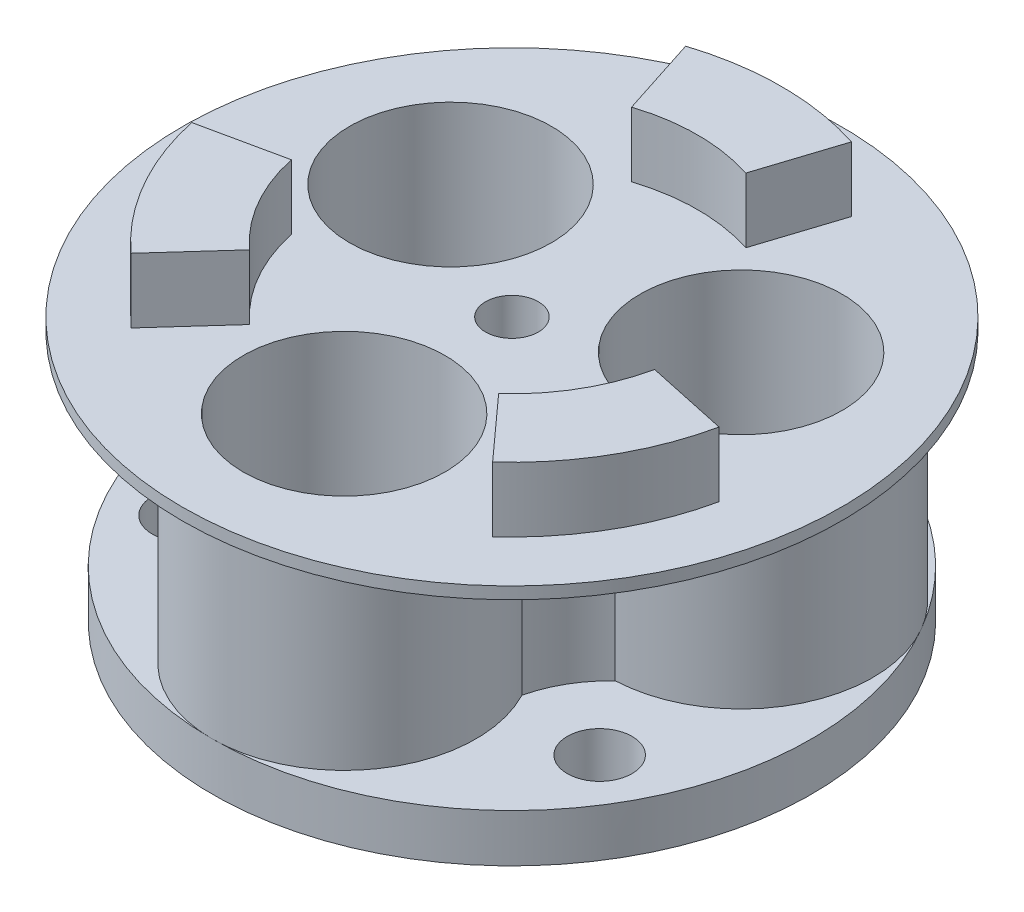
SolidWorks part; units mm, degrees
ref_plane "Front Plane" through (0, 0, 0) normal (0, 0, 1) x (1, 0, 0)
ref_plane "Top Plane" through (0, 0, 0) normal (0, 1, 0) x (1, 0, 0)
ref_plane "Right Plane" through (0, 0, 0) normal (1, 0, 0) x (0, 0, -1)
sketch "Sketch1" plane through (0, 0, 0) normal (0, 1, 0) x (1, 0, 0)
  line L0 (0, -55) -> (0, 55) construction
  circle A0 centre (0, 0) radius 27.5
  circle A1 centre (0, 0) radius 2.2
  circle A2 centre (0, -14) radius 8.425
  circle A3 centre (-12.1244, 7) radius 8.425
  circle A4 centre (12.1244, 7) radius 8.425
  point P14 (0, 0)
  dimension "D1" = 55
  dimension "D2" = 4.4
  dimension "D3" = 16.85
  dimension "D4" = 14
  dimension "D5" = 3
extrude "Boss-Extrude1" add sketch "Sketch1" along normal blind 22
ref_plane "Plane1" through (0, 4, 0) normal (0, 1, 0) x (1, 0, 0)
sketch "Sketch4" plane through (0, 22, 0) normal (0, 1, 0) x (1, 0, 0)
  line L0 (0, 0) -> (23.6709, -13.6664) construction
  line L1 (-22.0001, -4.7164) -> (-15.1556, -3.2491)
  line L2 (0, -55) -> (0, 55) construction
  line L3 (15.0846, -16.6945) -> (10.3916, -11.5006)
  line L4 (22.0001, -4.7164) -> (15.1556, -3.2491)
  line L5 (-15.0846, -16.6945) -> (-10.3916, -11.5006)
  line L6 (6.9155, 21.4109) -> (4.764, 14.7497)
  line L7 (-6.9155, 21.4109) -> (-4.764, 14.7497)
  circle A0 centre (0, 0) radius 22.5
  circle A2 centre (0, 0) radius 15.5
  point P23 (-1.3727, 0.446)
  point P24 (0, 0)
  dimension "D1" = 45
  dimension "D2" = 7
  dimension "D3" = 60
  dimension "D4" = 35.8
  dimension "D5" = 3
extrude "Boss-Extrude2" add sketch "Sketch4" along normal blind 5.4 contours A2 A0 | A2 A0 | L0 A2 L3 A0 | A2 L0 A0 L4 region at (17.8598, 22, 6.8736) region at (14.8826, 22, 12.0302) region at (-16.3712, 22, 9.4519) region at (0, 22, -18.9039)
sketch "Sketch5" plane through (0, 4, 0) normal (0, 1, 0) x (1, 0, 0)
  circle A0 centre (-12.1244, 7) radius 11
  circle A1 centre (0, 0) radius 22.5 construction
  circle A2 centre (0, 22.5) radius 10
  circle A3 centre (0, 0) radius 40.9893
  circle A4 centre (12.1244, 7) radius 11
  circle A5 centre (19.4856, -11.25) radius 10
  circle A6 centre (0, -14) radius 11
  circle A7 centre (-19.4856, -11.25) radius 10
  point P20 (0, 0)
  dimension "D1" = 22
  dimension "D2" = 20
  dimension "D3" = 45
  dimension "D4" = 3
extrude "Cut-Extrude1" cut sketch "Sketch5" along normal blind 17 contours A3 A7 A0 A2 A4 A5 A6 | A6 A5 A4 | A4 A2 A0 | A6 A7 A0 region at (0, 4, -22.8169) region at (-19.76, 4, 11.4085) region at (19.76, 4, 11.4085) region at (-39.8299, 4, 0)
sketch "Sketch6" plane through (0, 0, 0) normal (0, -1, 0) x (1, 0, 0)
  circle A0 centre (0, 0) radius 20 construction
  circle A1 centre (0, -20) radius 2.7
  circle A2 centre (-17.3205, 10) radius 2.7
  circle A3 centre (17.3205, 10) radius 2.7
  point P11 (0, 0)
  dimension "D1" = 40
  dimension "D2" = 5.4
  dimension "D3" = 3
extrude "Cut-Extrude2" cut sketch "Sketch6" against normal blind 5
sketch "Sketch7" plane through (0, 0, 0) normal (0, -1, 0) x (1, 0, 0)
  circle A0 centre (0, 0) radius 25
  circle A2 centre (0, 0) radius 33.7565
  circle M6 centre (0, 0) radius 27.5
  dimension "D1" = 50
extrude "Cut-Extrude6" cut sketch "Sketch7" against normal blind 4 contours A0 M6 | A2 M6 region at (-32.8017, 0, 0) region at (-26.7222, 0, 0)
